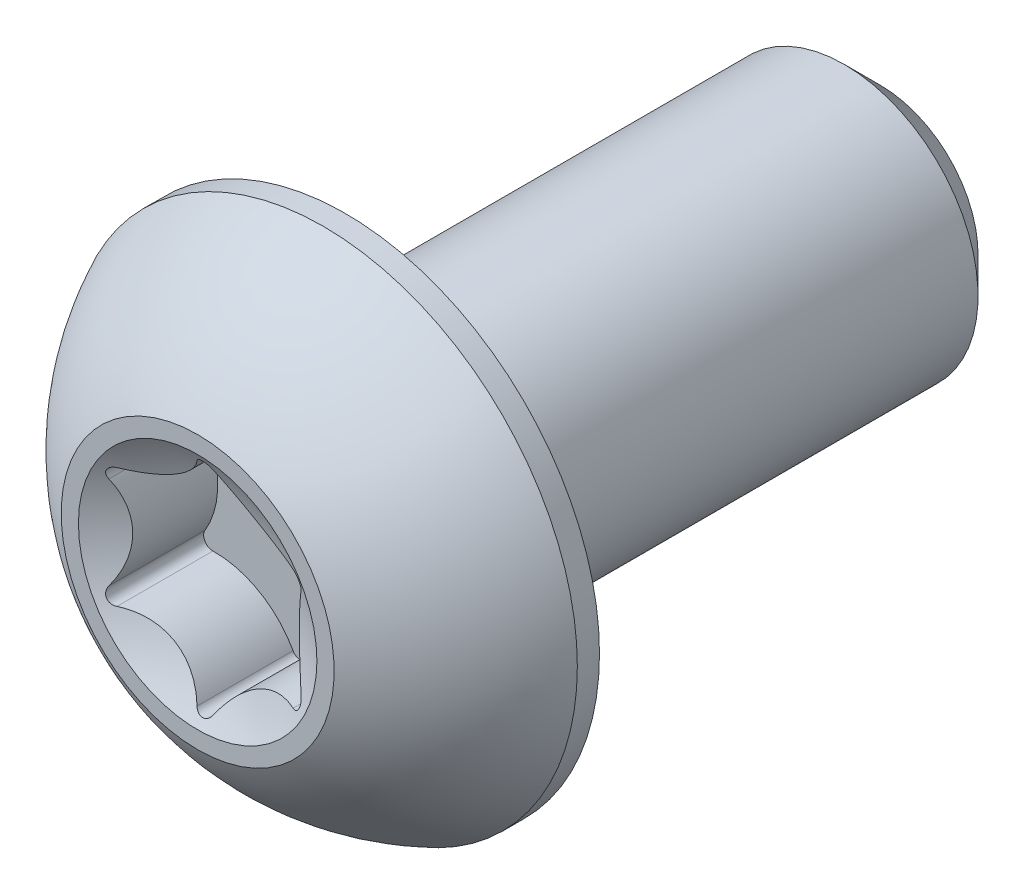
SolidWorks part; units mm, degrees
ref_plane "Front" through (0, 0, 0) normal (0, 0, 1) x (1, 0, 0)
ref_plane "Top" through (0, 0, 0) normal (0, 1, 0) x (1, 0, 0)
ref_plane "Right" through (0, 0, 0) normal (1, 0, 0) x (0, 0, -1)
sketch "Sketch1" plane through (0, 0, 0) normal (1, 0, 0) x (0, 0, -1)
  line L0 (0, 0) -> (6.38, 0) construction
  line L1 (0, 2.375) -> (0, 0) construction
  line L2 (1.38, 0) -> (1.38, 2.375) construction
  line L3 (6.38, 0) -> (6.38, 1.25) construction
  line L8 (6.3659, 1.2744) -> (6.5487, 0.9577)
  line L9 (6.605, 0.9577) -> (6.7878, 1.2744)
  line L10 (6.38, 1.25) -> (1.38, 1.25) construction
  line L11 (1.38, 2.375) -> (1.173, 2.375) construction
  line L12 (6.38, 0) -> (6.38, -1.25) construction
  line L13 (6.3519, 1.2987) -> (6.8019, 1.2987) construction
  line L14 (6.8019, 1.2987) -> (6.5769, 0.909) construction
  line L15 (6.5769, 0.909) -> (6.3519, 1.2987) construction
  line L16 (6.5769, 0.909) -> (6.5769, 0.9577) construction
  line L17 (6.5769, 1.2987) -> (6.5769, 1.25) construction
  line L18 (6.38, 1.25) -> (6.7737, 1.25) construction
  line L19 (6.3659, 1.2744) -> (6.7878, 1.2744)
  line L20 (6.5487, 0.9577) -> (6.605, 0.9577)
  arc A0 (0, 1.2754) -> (1.173, 2.375) centre (2.2975, 0) cw construction
  point P8 (0, 1.0379)
  point P19 (0.966, 0)
  point P21 (0, 0.7784)
  point P26 (5.255, -1.25)
  point P37 (6.5769, 1.25)
  point P39 (6.5769, 1.2744)
  point P42 (6.5769, 0.9577)
  dimension "Head Diameter" = 4.75
  dimension "Head Height" = 1.38
  dimension "Length" = 5
  dimension "Thread Size" = 2.5
  dimension "Approx Drive Size " = 2.0758
  dimension "Approx Screw Head Flat" = 0.207
  dimension "Approx Drive Depth" = 0.966
  dimension "Approx Drive Gap" = 0.2375
  dimension "Approx Min Drive Size" = 1.5568
  dimension "Thread Note" = 1.125
  dimension "Thread Pitch" = 0.45
  dimension "Pitch/8" = 0.0563
sketch "Sketch2" plane through (0, 0, 0) normal (1, 0, 0) x (0, 0, -1)
  line L0 (1.38, 2.375) -> (1.38, 1.25) construction
  line L1 (1.38, 0) -> (1.38, 2.375) construction
  line L2 (6.38, 1.25) -> (1.38, 1.25) construction
  line L3 (1.38, 1.25) -> (6.0425, 1.25)
  line L4 (6.38, 0.9125) -> (6.38, 0)
  line L5 (6.38, 0) -> (1.38, 0)
  line L6 (0, 0) -> (0, 1.2754) construction
  line L7 (1.173, 2.375) -> (1.38, 2.375) construction
  line L8 (6.0425, 1.25) -> (6.38, 0.9125)
  line L9 (1.38, 1.25) -> (1.38, 0)
  arc A0 (1.173, 2.375) -> (0, 1.2754) centre (2.2975, 0) ccw construction
  arc A1 (1.173, 2.375) -> (0, 1.2754) centre (2.2975, 0) ccw construction
  point P11 (6.38, 1.25)
  dimension "D1" = 0.3375
  dimension "D2" = 45
revolve "Revolve1" add sketch "Sketch2" angle 360 about L5
sketch "Sketch3" plane through (0, 0, 0) normal (1, 0, 0) x (0, 0, -1)
  line L0 (1.38, 0) -> (1.38, 2.375) construction
  line L1 (1.38, 2.375) -> (1.173, 2.375) construction
  line L2 (1.38, 0) -> (1.38, 2.375)
  line L3 (1.38, 2.375) -> (1.173, 2.375)
  line L4 (0, 1.2754) -> (0, 0)
  line L5 (0, 0) -> (1.38, 0)
  arc A0 (1.173, 2.375) -> (0, 1.2754) centre (2.2975, 0) ccw construction
  arc A1 (1.173, 2.375) -> (0, 1.2754) centre (2.2975, 0) ccw
revolve "Revolve2" add sketch "Sketch3" angle 360 about L5
combine bodies "Combine1" operation type add bodies to combine 114 109
sketch "Sketch4" plane through (0, 0, 0) normal (0, 0, 1) x (1, 0, 0)
  line L2 (0, 0) -> (-0.8988, 0.5189)
  line L3 (0, 0) -> (-1.2754, 0) construction
  line L4 (-0.7784, 0) -> (-0.7784, -0.4494) construction
  line L5 (0, 0) -> (-0.8988, -0.5189)
  line L6 (0, 0.1558) -> (-0.8988, 0.5189) construction
  circle A0 centre (0, 0) radius 1.0379 construction
  circle A1 centre (0, 0) radius 0.7784 construction
  circle A2 centre (0, 0) radius 2.375 construction
  arc A4 (-0.8981, -0.4324) -> (-0.8981, 0.4324) centre (-1.6191, 0) ccw
  arc A5 (-0.8988, 0.5189) -> (-0.8981, 0.4324) centre (-0.8249, 0.4763) ccw
  arc A6 (-0.8988, -0.5189) -> (-0.8981, -0.4324) centre (-0.8249, -0.4763) cw
  circle A7 centre (0, 0) radius 0.1558 construction
  circle A8 centre (0, 0) radius 1.2754 construction
  point P4 (-1.0379, 0)
  point P5 (-0.7784, 0)
  point P12 (0.8988, -0.5189)
  dimension "D4" = 0.8407
  dimension "D3" = 30
  dimension "D5" = 8
extrude "Cut-Extrude1" cut sketch "Sketch4" against normal blind 0.966
pattern_circular "CirPattern1" count 6 over 360 about axis through (0, 0, -6.38) along (0, 0, -1) of "Cut-Extrude1"
sketch "Sketch5" plane through (0, 0, 0) normal (1, 0, 0) x (0, 0, -1)
  line L0 (0, 0) -> (0.322, 0) construction
  line L1 (-1.7673, 2.0893) -> (-1.7673, -2.0893)
  line L2 (0, 0) -> (0.161, 0) construction
  line L3 (0, 1.2754) -> (0, -1.2754) construction
  line L4 (0, 1.2754) -> (0, 1.1144) construction
  arc A0 (-1.7673, -2.0893) -> (-1.7673, 2.0893) centre (-1.7673, 0) ccw
  dimension "D1" = 0.322
revolve "Cut-Revolve1" cut sketch "Sketch5" angle 360 about L1
split "Split1" [suppressed] bodies to split 113
sketch "Sketch6" [suppressed] plane through (0, 0, -6.38) normal (0, 0, -1) x (-1, 0, 0)
  circle A0 centre (0, 0) radius 1.25
curve "Helix/Spiral1" [suppressed] pitch 0.45 height 5.45 turns 12.1111
sketch "Sketch7" [suppressed] plane through (0, 0, 0) normal (1, 0, 0) x (0, 0, -1)
  line L0 (6.3659, 1.2744) -> (6.7878, 1.2744)
  line L1 (6.7878, 1.2744) -> (6.605, 0.9577)
  line L2 (6.605, 0.9577) -> (6.5487, 0.9577)
  line L3 (6.5487, 0.9577) -> (6.3659, 1.2744)
sweep "Cut-Sweep1" [suppressed] cut profiles "Sketch7" path "Helix/Spiral1"
sketch "Sketch8" [suppressed] plane through (0, 0, -1.38) normal (0, 0, -1) x (-1, 0, 0)
  circle A0 centre (0, 0) radius 1.25 construction
  circle A2 centre (0, 0) radius 1.3008
  dimension "D1" = 0.0508
extrude "Boss-Extrude1" [suppressed] add sketch "Sketch8" along normal up to next draft 20
equation "\"Approx Screw Head Flat@Sketch1\" = \"Head Height@Sketch1\" * .15"
equation "\"Approx Drive Depth@Sketch1\" = \"Head Height@Sketch1\" * .7"
equation "\"D1@Cut-Extrude1\" = \"Approx Drive Depth@Sketch1\""
equation "\"D1@Sketch5\" = \"Approx Drive Depth@Sketch1\" / 3"
equation "\"D1@Sketch2\" = \"Thread Pitch@Sketch1\" * .75"
equation "\"Approx Drive Gap@Sketch1\" = \"Head Diameter@Sketch1\" * .05"
equation "\"Approx Min Drive Size@Sketch1\" = \"Approx Drive Size @Sketch1\" * .75"
equation "\"Thread Note@Sketch1\" = \"Thread Pitch@Sketch1\" * 2.5"
equation "\"Pitch/8@Sketch1\" = \"Thread Pitch@Sketch1\" / 8"
equation "\"D4@Helix/Spiral1\" = \"Thread Pitch@Sketch1\""
equation "\"D3@Helix/Spiral1\" = \"Length@Sketch1\" + \"Thread Pitch@Sketch1\""
equation "\"Approx Drive Size @Sketch1\"  = \"Head Diameter@Sketch1\"*.437"
equation "\"D4@Sketch4\"=\"Approx Min Drive Size@Sketch1\"*.54"
